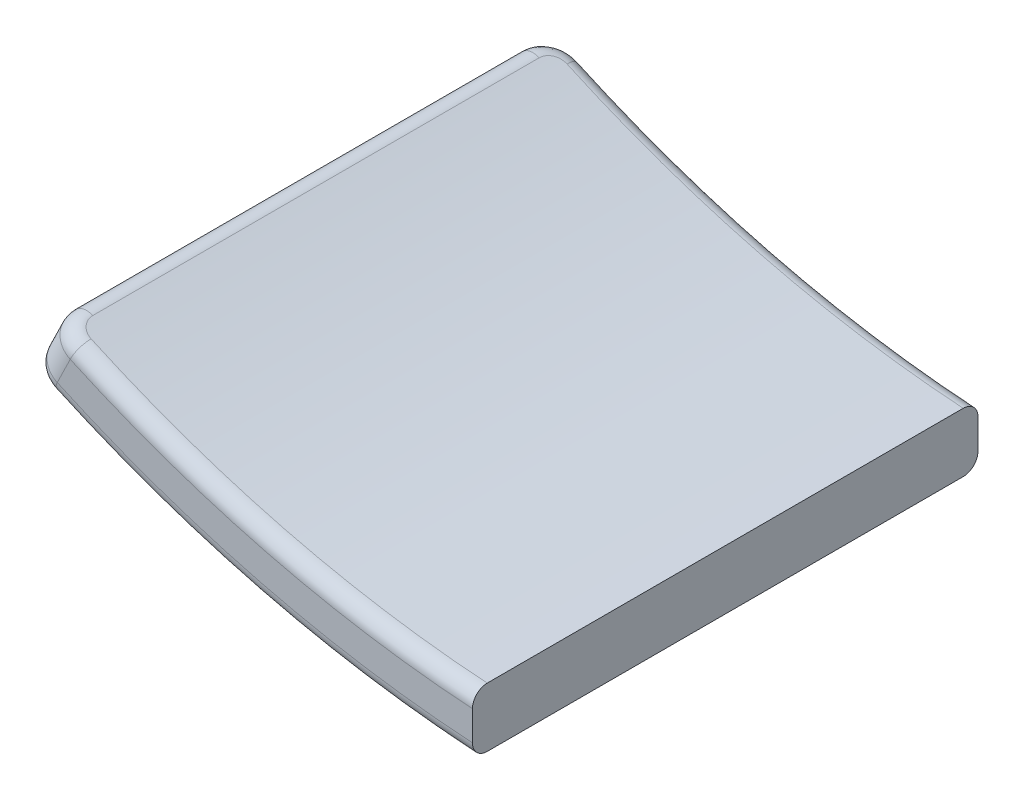
SolidWorks part; units mm, degrees
material "Polyurethane Foam Flexible"
ref_plane "Front Plane" through (0, 0, 0) normal (0, 0, 1) x (1, 0, 0)
ref_plane "Top Plane" through (0, 0, 0) normal (0, 1, 0) x (1, 0, 0)
ref_plane "Right Plane" through (0, 0, 0) normal (1, 0, 0) x (0, 0, -1)
sketch "Sketch1" plane through (0, 0, 0) normal (0, 0, 1) x (1, 0, 0)
  line L0 (-50.8, 241.8618) -> (-50.8, 190.9556)
  line L1 (-413.9908, 338.5903) -> (-436.2836, 292.943)
  line L2 (-50.8, -293.7629) -> (-50.8, 126.9246) construction
  line L4 (-38.1, -293.7629) -> (-38.1, -174.5629) construction
  arc A1 (-413.9908, 338.5903) -> (-50.8, 241.8618) centre (13.752, 1214.4469) ccw
  arc A2 (-436.2836, 292.943) -> (-50.8, 190.9556) centre (13.752, 1214.4469) ccw
  arc A3 (-436.2836, 292.943) -> (-0.1289, 189.0159) centre (13.752, 1214.4469) ccw construction
  arc A4 (-413.9908, 338.5903) -> (0.5587, 239.8112) centre (13.752, 1214.4469) ccw construction
  arc A5 (-413.9908, 338.5903) -> (-0.0449, 239.8196) centre (13.752, 1214.4469) ccw construction
  dimension "D2" = 50.8
extrude "Boss-Extrude1" add sketch "Sketch1" against normal up to surface (434.6 mm away)
fillet "Fillet1" radius 25.4 2 edges at (-425.1372, 315.7666, 0) (-425.1372, 315.7666, -434.6)
fillet "Fillet2" radius 12.7 10 edges at (-236.2478, 219.8608, -434.6) (-431.2757, 290.5141, -425.0671) (-436.2836, 292.943, -217.3) (-427.6964, 288.7986, -5.5642) (-236.2478, 219.8608, 0) (-405.4024, 334.4478, -429.036) (-224.8073, 269.3658, -434.6) (-224.8073, 269.3658, 0) (-408.9826, 336.1621, -9.5329) (-413.9908, 338.5903, -217.3)
